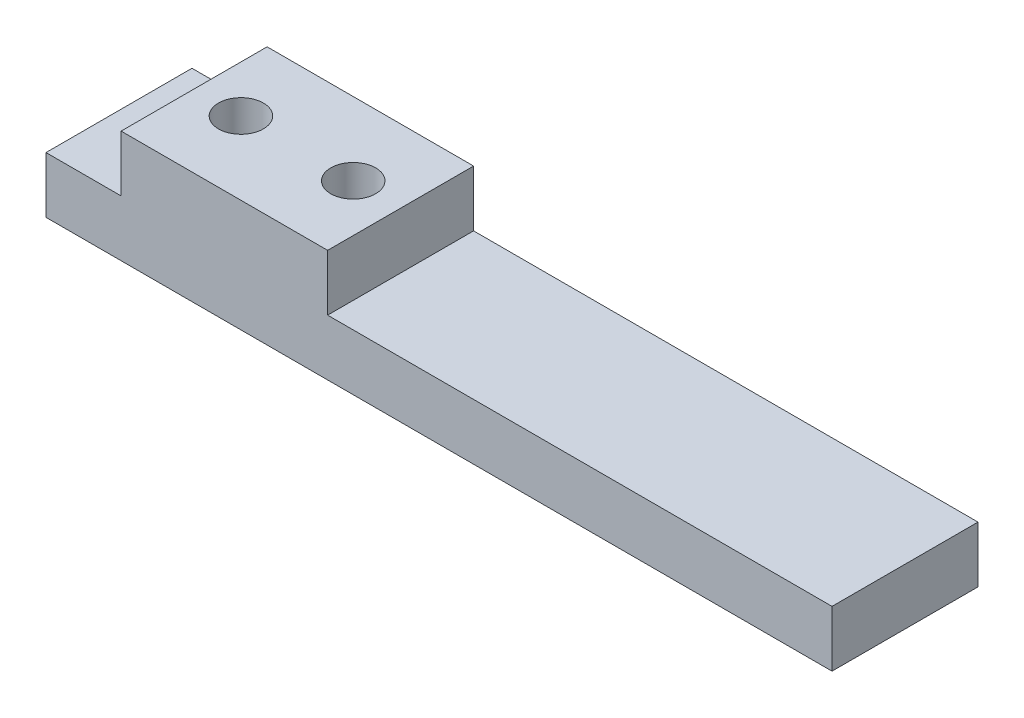
SolidWorks part; units mm, degrees
material "6061-T6 (SS)"
ref_plane "Front Plane" through (0, 0, 0) normal (0, 0, 1) x (1, 0, 0)
ref_plane "Top Plane" through (0, 0, 0) normal (0, 1, 0) x (1, 0, 0)
ref_plane "Right Plane" through (0, 0, 0) normal (1, 0, 0) x (0, 0, -1)
sketch "Sketch1" plane through (0, 0, 0) normal (0, 1, 0) x (1, 0, 0)
  line L1 (-35, 6.5) -> (35, 6.5)
  line L2 (-35, 6.5) -> (-35, -6.5)
  line L3 (-35, -6.5) -> (35, -6.5)
  line L4 (35, 6.5) -> (35, -6.5)
  line L5 (-35, 6.5) -> (35, -6.5) construction
  line L6 (-35, -6.5) -> (35, 6.5) construction
  point P0 (0, 0)
  dimension "D1" = 13
  dimension "D2" = 70
extrude "Boss-Extrude1" add sketch "Sketch1" along normal blind 5
sketch "Sketch2" plane through (0, 5, 0) normal (0, 1, 0) x (1, 0, 0)
  line L6 (-41.2697, 0) -> (45.9035, 0) construction
  line L7 (35, 6.5) -> (-35, 6.5) construction
  line L8 (-28.3096, 6.5) -> (-9.9192, 6.5)
  line L9 (-28.3096, 6.5) -> (-28.3096, -6.5)
  line L10 (-28.3096, -6.5) -> (-9.9192, -6.5)
  line L11 (-9.9192, 6.5) -> (-9.9192, -6.5)
  line L12 (-35, -6.5) -> (35, -6.5) construction
  circle A0 centre (-24.1413, 0) radius 2
  circle A1 centre (-14.1413, 0) radius 2
  dimension "D1" = 4
  dimension "D2" = 10
extrude "Cut-Extrude1" cut sketch "Sketch2" against normal through all contours L6 A0 | A0 L6 | L6 A1 | A1 L6 region at (-24.1413, 5, -0.8488) region at (-24.1413, 5, 0.8488) region at (-14.1413, 5, -0.8488) region at (-14.1413, 5, 0.8488)
extrude "Boss-Extrude3" add sketch "Sketch2<3>" along normal blind 5
sketch "Sketch2<3>" plane through (0, 5, 0) normal (0, 1, 0) x (1, 0, 0) same geometry as "Sketch2"
